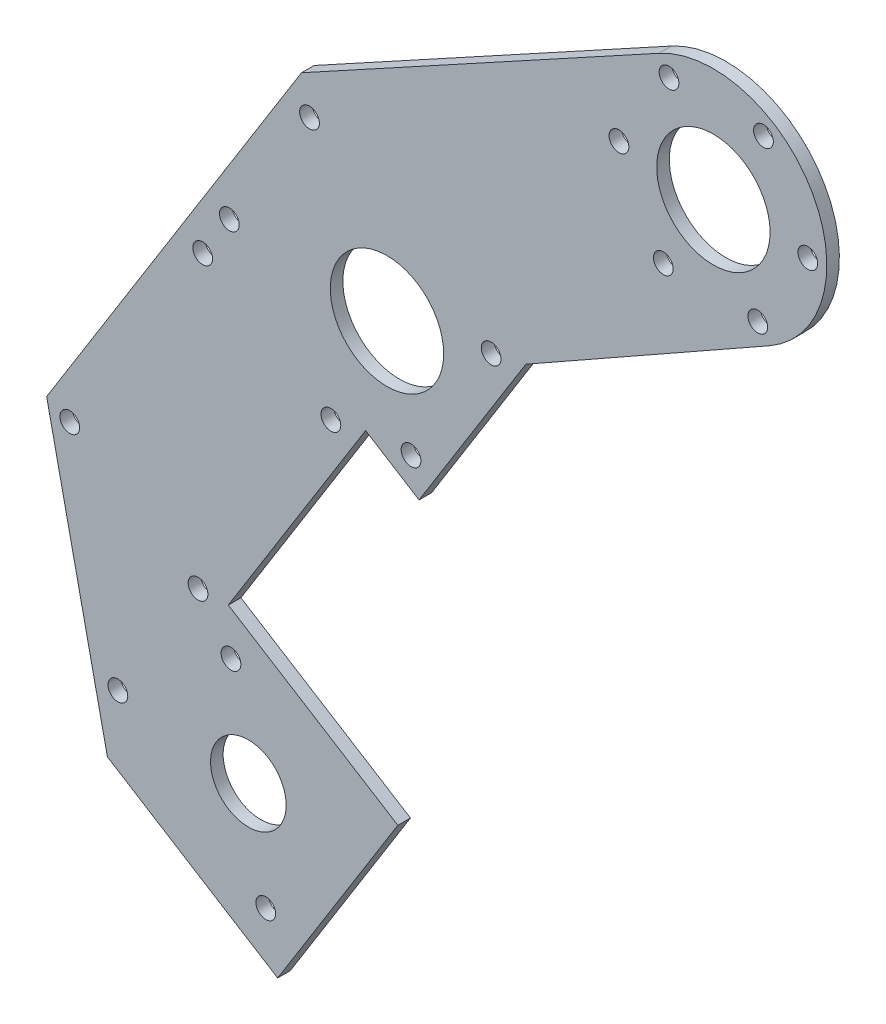
SolidWorks part; units mm, degrees
ref_plane "Front Plane" through (0, 0, 0) normal (0, 0, 1) x (1, 0, 0)
ref_plane "Top Plane" through (0, 0, 0) normal (0, 1, 0) x (1, 0, 0)
ref_plane "Right Plane" through (0, 0, 0) normal (1, 0, 0) x (0, 0, -1)
sketch "Sketch1" plane through (0, 0, -14.1946) normal (0, 0, 1) x (1, 0, 0)
  line L0 (-11.4036, 461.0409) -> (18.8813, 509.5069)
  line L1 (-54.3079, 487.8505) -> (-69.6155, 558.824)
  line L2 (18.8813, 509.5069) -> (-23.8465, 536.2061)
  line L3 (10.7592, 591.5868) -> (-157.4902, 322.3315) construction
  line L4 (-11.4036, 461.0409) -> (-54.3079, 487.8505)
  line L5 (-69.6155, 558.824) -> (-5.4017, 661.5875)
  line L6 (-23.8465, 536.2061) -> (10.7592, 591.5868)
  line L8 (-115.7964, 730.5698) -> (51.1419, 626.2552) construction
  line L9 (-142.7163, 687.4889) -> (24.222, 583.1743) construction
  line L10 (51.1419, 626.2552) -> (112.462, 660.9373)
  line L11 (10.7592, 591.5868) -> (24.222, 583.1743)
  line L13 (24.222, 583.1743) -> (51.1419, 626.2552)
  line L16 (-5.4017, 661.5875) -> (84.678, 710.8773)
  line L17 (16.1415, 618.1747) -> (-107.7159, 695.5694) construction
  line L18 (3.7388, 485.2739) -> (-32.2498, 508.4981) construction
  circle A2 centre (16.1415, 618.1747) radius 14.2875
  circle A3 centre (-18.7876, 499.8107) radius 9.525
  circle A5 centre (98.3945, 685.8096) radius 14.2875
  arc A7 (112.462, 660.9373) -> (84.678, 710.8773) centre (98.3945, 685.8096) ccw
  circle A8 centre (-107.7159, 695.5694) radius 215.011 construction
  point P33 (98.3945, 685.8096)
extrude "Boss-Extrude1" add sketch "Sketch1" along normal blind 3.175
sketch "Sketch17" plane through (0, 0, -11.0196) normal (0, 0, 1) x (1, 0, 0)
  line L0 (-14.4068, 474.7913) -> (-18.7876, 499.8107) construction
  line L1 (-18.7876, 499.8107) -> (-23.1685, 524.83) construction
  line L2 (16.1415, 618.1747) -> (37.6819, 604.7147) construction
  line L12 (24.222, 583.1743) -> (51.1419, 626.2552) construction
  line L13 (37.6819, 604.7147) -> (27.587, 588.5594) construction
  line L14 (27.587, 588.5594) -> (22.2019, 591.9244) construction
  line L15 (22.2019, 591.9244) -> (-28.9566, 623.8918) construction
  line L16 (-5.4017, 661.5875) -> (-69.6155, 558.824) construction
  line L17 (-28.9566, 623.8918) -> (-23.5715, 620.5268) construction
  line L18 (-23.5715, 620.5268) -> (-3.3816, 652.8374) construction
  line L19 (-3.3816, 652.8374) -> (42.3918, 624.2351) construction
  line L20 (10.7592, 591.5868) -> (5.3741, 594.9518) construction
  line L21 (5.3741, 594.9518) -> (-31.4748, 535.9811) construction
  line L22 (-31.4748, 535.9811) -> (-51.6648, 503.6705) construction
  line L23 (5.3741, 594.9518) -> (2.0091, 589.5667) construction
  line L24 (-31.4748, 535.9811) -> (-63.7855, 556.1711) construction
  line L25 (2.0091, 589.5667) -> (-30.3015, 609.7566) construction
  circle A0 centre (-18.7876, 499.8107) radius 25.4
hole_wizard "#10 Clearance Hole2" positions "Sketch20" profile "Sketch21" hole size "#10" standard "ANSI Inch" end condition through all
sketch "Sketch20" plane through (0, 0, -11.0196) normal (0, 0, 1) x (1, 0, 0)
  point P0 (-23.1685, 524.83)
  point P3 (-14.4068, 474.7913)
  point P24 (-3.3816, 652.8374)
  point P27 (42.3918, 624.2351)
  point P30 (22.2019, 591.9244)
  point P33 (-23.5715, 620.5268)
  point P42 (-31.4748, 535.9811)
  point P45 (-63.7855, 556.1711)
  point P48 (-51.6648, 503.6705)
  point P54 (2.0091, 589.5667)
  point P57 (-30.3015, 609.7566)
sketch "Sketch21" plane through (-23.1685, 524.83, -11.0196) normal (1, 0, 0) x (0, -1, 0)
  line L0 (0, 0) -> (0, 3.175)
  line L1 (0, 3.175) -> (2.4892, 3.175)
  line L2 (2.4892, 3.175) -> (2.4892, 0)
  line L5 (2.4892, 0) -> (0, 0)
  line L11 (0, -6.35) -> (0, 107.95) construction
  dimension "Thru Hole Dia." = 4.9784
  dimension "Thru Hole Depth" = 3.175
sketch "Sketch22" plane through (0, 0, -11.0196) normal (0, 0, 1) x (1, 0, 0)
  line L0 (98.3945, 685.8096) -> (111.0132, 706.0038) construction
  line L2 (111.0132, 706.0038) -> (87.2152, 706.8348) construction
  line L3 (87.2152, 706.8348) -> (74.5965, 686.6407) construction
  line L4 (74.5965, 686.6407) -> (85.7758, 665.6155) construction
  line L5 (85.7758, 665.6155) -> (109.5738, 664.7845) construction
  line L6 (109.5738, 664.7845) -> (122.1925, 684.9786) construction
  line L7 (122.1925, 684.9786) -> (111.0132, 706.0038) construction
  circle A0 centre (98.3945, 685.8096) radius 23.8125 construction
hole_wizard "#10 Clearance Hole3" positions "Sketch23" profile "Sketch24" hole size "#10" standard "ANSI Inch" end condition through all
sketch "Sketch23" plane through (0, 0, -11.0196) normal (0, 0, 1) x (1, 0, 0)
  point P0 (111.0132, 706.0038)
  point P3 (122.1925, 684.9786)
  point P6 (109.5738, 664.7845)
  point P9 (85.7758, 665.6155)
  point P12 (74.5965, 686.6407)
  point P15 (87.2152, 706.8348)
sketch "Sketch24" plane through (111.0132, 706.0038, -11.0196) normal (1, 0, 0) x (0, -1, 0)
  line L0 (0, 0) -> (0, 3.175)
  line L1 (0, 3.175) -> (2.4892, 3.175)
  line L2 (2.4892, 3.175) -> (2.4892, 0)
  line L5 (2.4892, 0) -> (0, 0)
  line L11 (0, -6.35) -> (0, 107.95) construction
  dimension "Thru Hole Dia." = 4.9784
  dimension "Thru Hole Depth" = 3.175
